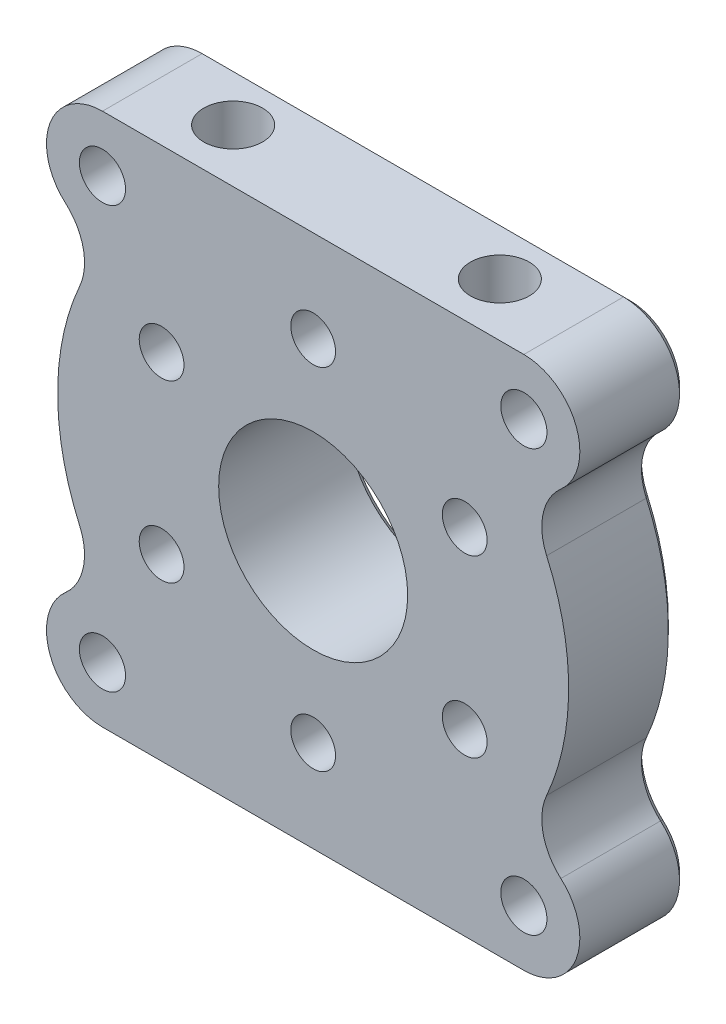
SolidWorks part; units mm, degrees
material "6061-T6 (SS)"
ref_plane "Front Plane" through (0, 0, 0) normal (0, 0, 1) x (1, 0, 0)
ref_plane "Top Plane" through (0, 0, 0) normal (0, 1, 0) x (1, 0, 0)
ref_plane "Right Plane" through (0, 0, 0) normal (1, 0, 0) x (0, 0, -1)
sketch "Sketch1" plane through (0, 0, 0) normal (0, 0, 1) x (1, 0, 0)
  line L1 (-15.0495, -19.05) -> (15.0495, -19.05)
  line L2 (-19.05, -15.0495) -> (-19.05, 15.0495)
  line L3 (-15.0495, 19.05) -> (15.0495, 19.05)
  line L4 (19.05, -15.0495) -> (19.05, 15.0495)
  line L5 (-19.05, -19.05) -> (19.05, 19.05) construction
  line L6 (-19.05, 19.05) -> (19.05, -19.05) construction
  line L7 (-15.0495, -15.0495) -> (15.0495, -15.0495) construction
  line L8 (-15.0495, -15.0495) -> (-15.0495, 15.0495) construction
  line L9 (-15.0495, 15.0495) -> (15.0495, 15.0495) construction
  line L10 (15.0495, -15.0495) -> (15.0495, 15.0495) construction
  line L11 (-15.0495, -15.0495) -> (15.0495, 15.0495) construction
  line L12 (-15.0495, 15.0495) -> (15.0495, -15.0495) construction
  arc A0 (-15.0495, -19.05) -> (-19.05, -15.0495) centre (-15.0495, -15.0495) cw
  arc A1 (15.0495, -19.05) -> (19.05, -15.0495) centre (15.0495, -15.0495) ccw
  arc A2 (15.0495, 19.05) -> (19.05, 15.0495) centre (15.0495, 15.0495) cw
  arc A3 (-19.05, 15.0495) -> (-15.0495, 19.05) centre (-15.0495, 15.0495) cw
  point P0 (0, 0)
  point P5 (0, 0)
  dimension "D4" = 4.0005
  dimension "D1" = 38.1
  dimension "D2" = 30.099
  dimension "D3" = 4.0005
extrude "Boss-Extrude1" add sketch "Sketch1" along normal blind 7.62
sketch "Sketch2" plane through (0, 0, 7.62) normal (0, 0, 1) x (1, 0, 0)
  circle A0 centre (0, 0) radius 6.75
  dimension "D1" = 13.5
extrude "Cut-Extrude1" cut sketch "Sketch2" against normal through all
sketch "Sketch3" plane through (0, 0, 0) normal (0, 0, -1) x (-1, 0, 0)
  line L0 (8.0703, 10.1917) -> (10.7904, 12.9118)
  line L1 (12.9118, 10.7904) -> (10.7904, 12.9118)
  line L2 (12.9118, 10.7904) -> (10.1917, 8.0703)
  line L4 (19.05, 19.05) -> (-19.05, -19.05) construction
  arc A0 (8.0703, 10.1917) -> (10.1917, 8.0703) centre (0, 0) ccw
  circle A1 centre (0, 0) radius 6.75 construction
  circle A2 centre (0, 0) radius 6.75
  point P7 (11.8511, 11.8511)
  dimension "D1" = 26
  dimension "D2" = 16.76
  dimension "D3" = 3
extrude "Boss-Extrude2" add sketch "Sketch3" along normal blind 2
pattern_circular "CirPattern1" count 4 over 360 about axis through (0, 0, 0) along (0, 0, 1) of "Boss-Extrude2"
cosmetic thread "Hole Thread2" parameters "D2"=4
cosmetic thread "Hole Thread3" parameters "D2"=4
cosmetic thread "Hole Thread4" parameters "D2"=4
sketch "Sketch8" plane through (0, 0, -2) normal (0, 0, -1) x (-1, 0, 0)
  line L0 (8.0703, 10.1917) -> (10.1917, 8.0703) construction
  line L1 (8.6091, 10.7305) -> (10.7305, 8.6091) construction
  line L2 (10.7904, 12.9118) -> (8.0703, 10.1917) construction
  line L3 (10.1917, 8.0703) -> (12.9118, 10.7904) construction
  circle A0 centre (7.4866, 11.853) radius 1.5875
  circle A1 centre (11.853, 7.4866) radius 1.5875
  dimension "D1" = 3.175
  dimension "D2" = 0.762
extrude "Cut-Extrude2" cut sketch "Sketch8" against normal up to surface (2 mm away) contours A0 | A1 up to face at (0, 0, 0)
fillet "Fillet3" radius 1.27 2 edges at (-5.9242, 11.5717, -1) (-11.5717, 5.9242, -1)
hole_wizard "M4 Tapped Hole1" positions "Sketch6" profile "Sketch5" tap size "M4" standard "ISO" end condition through all
sketch "Sketch6" plane through (0, 0, 0) normal (0, 0, -1) x (-1, 0, 0)
  point P0 (15.0495, 15.0495)
sketch "Sketch5" plane through (-15.0495, 15.0495, 0) normal (1, 0, 0) x (0, 1, 0)
  line L0 (0, 0) -> (0, 7.62)
  line L1 (0, 7.62) -> (1.65, 7.62)
  line L2 (1.65, 7.62) -> (1.65, 0)
  line L5 (1.65, 0) -> (0, 0)
  line L11 (0, -6.35) -> (0, 107.95) construction
  dimension "Thru Tap Drill Dia." = 3.3
  dimension "Thru Tap Drill Depth" = 7.62
cosmetic thread "Hole Thread1" parameters "D2"=4
pattern_circular "CirPattern3" count 4 over 360 about axis through (0, 0, 0) along (0, 0, 1) of "Cut-Extrude2", "M4 Tapped Hole1", "Fillet3"
cosmetic thread "Hole Thread5" parameters "D2"=4
cosmetic thread "Hole Thread6" parameters "D2"=4
cosmetic thread "Hole Thread7" parameters "D2"=4
fillet "Fillet2" radius 1.5875 8 edges at (-8.0703, 10.1917, -1) (-10.1917, 8.0703, -1) (-10.1917, -8.0703, -1) (-8.0703, -10.1917, -1) (8.0703, -10.1917, -1) (10.1917, -8.0703, -1) (10.1917, 8.0703, -1) (8.0703, 10.1917, -1)
sketch "Sketch9" plane through (0, 19.05, 0) normal (0, 1, 0) x (1, 0, 0)
  line L0 (-9.525, -3.81) -> (9.525, -3.81) construction
  line L1 (0, -7.62) -> (0, 0) construction
  line L5 (15.0495, -7.62) -> (-15.0495, -7.62) construction
  point P3 (0, -3.81)
  dimension "D1" = 19.05
hole_wizard "M5 Tapped Hole1" positions "Sketch12" profile "Sketch11" tap size "M5" standard "ISO"
sketch "Sketch12" plane through (0, 19.05, 0) normal (0, 1, 0) x (1, 0, 0)
  point P0 (-9.525, -3.81)
  point P3 (9.525, -3.81)
sketch "Sketch11" plane through (-9.525, 19.05, 3.81) normal (1, 0, 0) x (0, 0, 1)
  line L0 (0, 0) -> (0, 9.2618)
  line L1 (0, 9.2618) -> (2.1, 8)
  line L2 (2.1, 8) -> (2.1, 0)
  line L5 (2.1, 0) -> (0, 0)
  line L10 (0, 9.2618) -> (-2.1, 8) construction
  line L11 (0, -6.35) -> (0, 107.95) construction
  dimension "Tap Drill Dia." = 4.2
  dimension "Tap Drill Depth" = 8
  dimension "Drill Angle" = 118
cosmetic thread "Hole Thread8" parameters "D1"=10.0076, "D2"=5
cosmetic thread "Hole Thread9" parameters "D1"=10.0076, "D2"=5
mirror "Mirror1" about plane through (0, 0, 0) normal (0, 1, 0) of "M5 Tapped Hole1"
cosmetic thread "Hole Thread10" parameters "D1"=10.0076, "D2"=5
cosmetic thread "Hole Thread11" parameters "D1"=10.0076, "D2"=5
sketch "Sketch14" plane through (0, 0, 0) normal (0, 0, -1) x (-1, 0, 0)
  circle A0 centre (0, 0) radius 12.5 construction
  point P3 (0, 12.5)
  dimension "D1" = 25
hole_wizard "CBORE for M3 Hex Socket Head Cap Screw2" positions "Sketch18" profile "Sketch17" counterbore size "M3" standard "ISO" end condition through all
sketch "Sketch18" plane through (0, 0, -2) normal (0, 0, -1) x (-1, 0, 0)
  point P0 (0, 12.5)
sketch "Sketch17" plane through (0, 12.5, -2) normal (1, 0, 0) x (0, 1, 0)
  line L0 (0, 0) -> (0, 9.62)
  line L1 (0, 9.62) -> (1.6, 9.62)
  line L3 (1.6, 9.62) -> (1.6, 5.4)
  line L4 (1.6, 5.4) -> (3.25, 5.4)
  line L5 (3.25, 5.4) -> (3.25, 0)
  line L7 (3.25, 0) -> (0, 0)
  line L11 (0, -6.35) -> (0, 107.95) construction
  dimension "Thru Hole Dia." = 3.2
  dimension "Thru Hole Depth" = 9.62
  dimension "C'Bore Dia." = 6.5
  dimension "C'Bore Depth" = 5.4
pattern_circular "CirPattern4" count 6 over 360 about axis through (0, 0, 0) along (0, 0, 1) of "CBORE for M3 Hex Socket Head Cap Screw2"
sketch "Sketch19" plane through (0, 0, 7.62) normal (0, 0, 1) x (1, 0, 0)
  line L0 (19.05, -15.0495) -> (19.05, 15.0495) construction
  line L1 (19.05, -15.0495) -> (19.05, 15.0495)
  arc A1 (19.05, -15.0495) -> (17.6905, -12.0446) centre (15.0495, -15.0495) ccw
  arc A2 (17.6905, 12.0446) -> (19.05, 15.0495) centre (15.0495, 15.0495) ccw
  arc A3 (17.6905, 12.0446) -> (16.676, 7.4145) centre (20.3314, 9.0398) ccw
  arc A4 (16.676, -7.4145) -> (17.6905, -12.0446) centre (20.3314, -9.0398) ccw
  arc A5 (16.676, -7.4145) -> (16.676, 7.4145) centre (0, 0) ccw
  dimension "D1" = 18.25
extrude "Cut-Extrude3" cut sketch "Sketch19" against normal through all
mirror "Mirror2" about plane through (0, 0, 0) normal (1, 0, 0) of "Cut-Extrude3"
chamfer "Chamfer1" distance 0.5 angle 45 49 edges at (18.7928, -16.4607, 0) (0, -19.05, 0) (-18.7928, -16.4607, 0) (-4.3506, 12.2504, -2) (-6.8139, 10.4151, -2) (-5.787, 11.5606, -2) (-6.8139, -10.4151, -2) (6.8139, 10.4151, -2) (-5.787, -11.5606, -2) (4.3506, -12.2504, -2) (6.8139, -10.4151, -2) (5.787, -11.5606, -2) (5.787, 11.5606, -2) (-11.8511, 11.8511, -2) (-9.6998, 11.8211, -2) (-9.6998, -11.8211, -2) (9.6998, 11.8211, -2) (-8.2832, -10.4798, -2) (8.2832, -10.4798, -2) (8.2832, 10.4798, -2) (-8.2832, 10.4798, -2) (-6.75, 0, -2) (4.3506, 12.2504, -2) (0, 9.25, -2) (13, 0, -2) (7.619, 5.7188, -2) (12.2266, -10.1053, -2) (7.619, -5.7188, -2) (-4.3506, -12.2504, -2) (0, -9.25, -2) (-13, 0, -2) (-7.619, -5.7188, -2) (-12.2266, 10.1053, -2) (-7.619, 5.7188, -2) (16.4236, -9.896, 0) (18.25, 0, 0) (16.4236, 9.896, 0) (-16.4236, 9.896, 0) (-18.25, 0, 0) (-16.4236, -9.896, 0) (11.8511, 11.8511, -2) (12.2266, 10.1053, -2) (11.8511, -11.8511, -2) (9.6998, -11.8211, -2) (-11.8511, -11.8511, -2) (-12.2266, -10.1053, -2) (-18.7928, 16.4607, 0) (0, 19.05, 0) (18.7928, 16.4607, 0)
